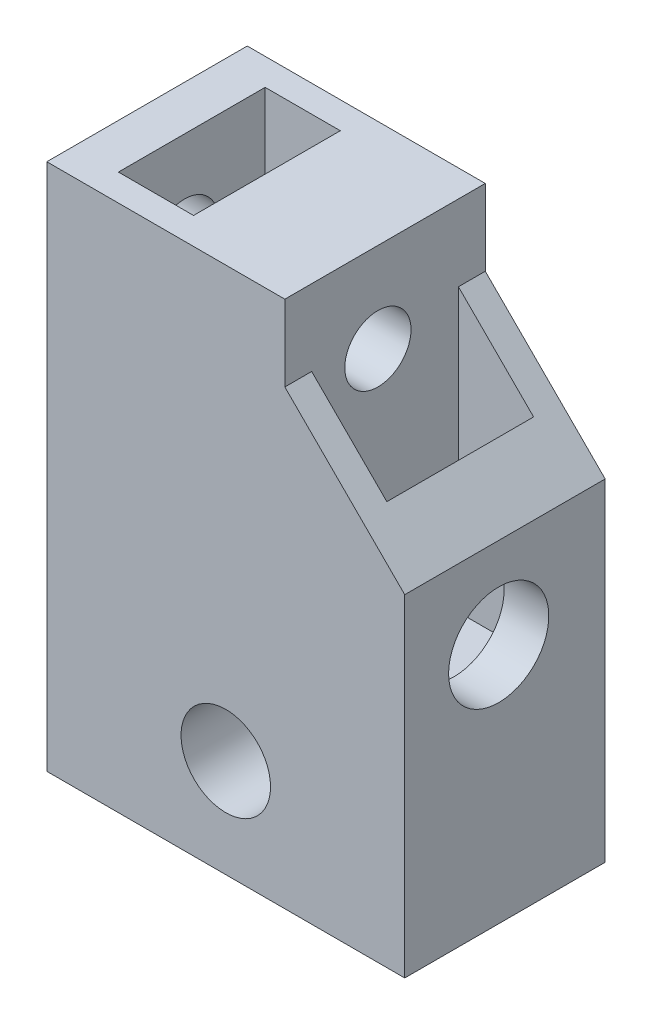
SolidWorks part; units mm, degrees
material "ABS PC"
ref_plane "Front Plane" through (0, 0, 0) normal (0, 0, 1) x (1, 0, 0)
ref_plane "Top Plane" through (0, 0, 0) normal (0, 1, 0) x (1, 0, 0)
ref_plane "Right Plane" through (0, 0, 0) normal (1, 0, 0) x (0, 0, -1)
sketch "Sketch6" plane through (0, 0, 0) normal (0, 1, 0) x (1, 0, 0)
  line L0 (0, 0) -> (0, 11.2)
  line L1 (0, 0) -> (20, 0)
  line L2 (0, 11.2) -> (20, 11.2)
  line L3 (20, 0) -> (20, 11.2)
  dimension "D1" = 20
  dimension "D2" = 11.2
extrude "Boss-Extrude2" add sketch "Sketch6" along normal blind 29.5
sketch "Sketch7" plane through (0, 0, 0) normal (0, 0, 1) x (1, 0, 0)
  line L0 (0, 0) -> (20, 0) construction
  line L1 (0, 29.5) -> (0, 0) construction
  circle A0 centre (10, 5.5) radius 2.5
  dimension "D1" = 5
  dimension "D2" = 5.5
  dimension "D3" = 10
extrude "Cut-Extrude4" cut sketch "Sketch7" against normal through all
sketch "Sketch8" plane through (0, 0, 0) normal (-1, 0, 0) x (0, 0, 1)
  line L1 (-11.2, 0) -> (0, 0) construction
  line L2 (0, 29.5) -> (0, 0) construction
  circle A0 centre (-5.25, 13.5) radius 2.8
  dimension "D1" = 5.6
  dimension "D3" = 13.5
  dimension "D2" = 5.25
extrude "Cut-Extrude5" cut sketch "Sketch8" against normal through all
sketch "Sketch9" plane through (0, 29.5, 0) normal (0, 1, 0) x (1, 0, 0)
  line L0 (2.5, 9.7) -> (6.7, 9.7)
  line L1 (2.5, 9.7) -> (2.5, 1.5)
  line L2 (6.7, 9.7) -> (6.7, 1.5)
  line L3 (2.5, 1.5) -> (6.7, 1.5)
  line L4 (13.3, 9.7) -> (17.5, 9.7)
  line L5 (13.3, 9.7) -> (13.3, 1.5)
  line L6 (17.5, 9.7) -> (17.5, 1.5)
  line L7 (13.3, 1.5) -> (17.5, 1.5)
  line L8 (0, 11.2) -> (0, 0) construction
  line L9 (20, 0) -> (20, 11.2) construction
  line L10 (20, 11.2) -> (0, 11.2) construction
  dimension "D1" = 1.5
  dimension "D2" = 4.2
  dimension "D3" = 2.5
  dimension "D4" = 2.5
  dimension "D5" = 8.2
extrude "Cut-Extrude6" cut sketch "Sketch9" against normal blind 20
sketch "Sketch11" plane through (20, 0, 0) normal (1, 0, 0) x (0, 0, -1)
  line L1 (11.2, 29.5) -> (11.2, 0) construction
  circle A0 centre (5.2, 24.5) radius 1.85
  circle A1 centre (5.25, 13.5) radius 2.8 construction
  dimension "D1" = 3.7
  dimension "D2" = 11
  dimension "D3" = 6
extrude "Cut-Extrude8" cut sketch "Sketch11" against normal through all
sketch "Sketch12" plane through (20, 0, 0) normal (1, 0, 0) x (0, 0, -1)
  line L0 (11.2, 29.5) -> (11.2, 18.5)
  line L1 (11.2, 29.5) -> (0, 29.5)
  line L2 (11.2, 18.5) -> (0, 18.5)
  line L3 (0, 29.5) -> (0, 18.5)
  line L4 (11.2, 29.5) -> (11.2, 0) construction
  line L5 (0, 29.5) -> (0, 0) construction
  circle A0 centre (5.25, 13.5) radius 2.8 construction
  dimension "D1" = 5
extrude "Cut-Extrude9" cut sketch "Sketch12" against normal up to vertex (6.7 mm away) up to point (13.3, 29.5, -9.7)
chamfer "Chamfer1" distance 6.75 angle 45 1 edges at (13.3, 18.5, -10.45)
